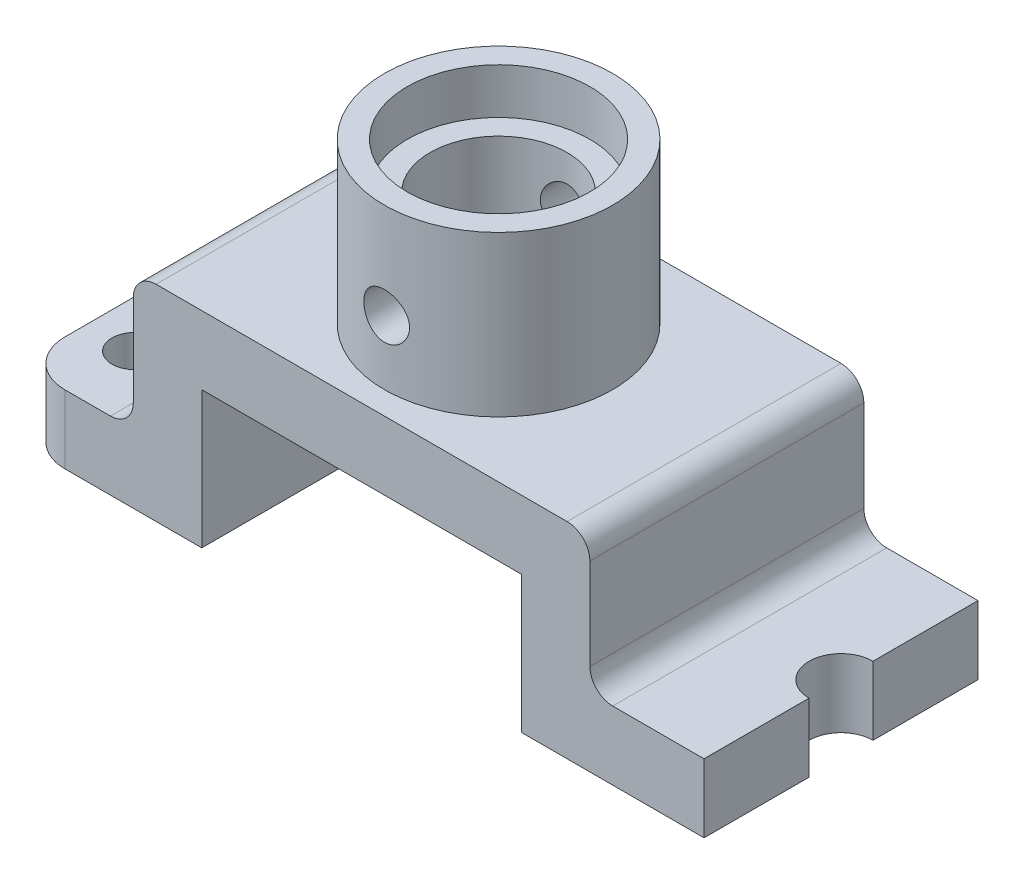
SolidWorks part; units mm, degrees
ref_plane "Front Plane" through (0, 0, 0) normal (0, 0, 1) x (1, 0, 0)
ref_plane "Top Plane" through (0, 0, 0) normal (0, 1, 0) x (1, 0, 0)
ref_plane "Right Plane" through (0, 0, 0) normal (1, 0, 0) x (0, 0, -1)
sketch "Sketch1" plane through (0, 0, 0) normal (0, 0, 1) x (1, 0, 0)
  line L1 (-75, 22.5) -> (75, 22.5)
  line L2 (-75, 22.5) -> (-75, -22.5)
  line L3 (-75, -22.5) -> (75, -22.5)
  line L4 (75, 22.5) -> (75, -22.5)
  line L5 (-75, 22.5) -> (75, -22.5) construction
  line L6 (-75, -22.5) -> (75, 22.5) construction
  point P0 (0, 0)
  dimension "D1" = 45
  dimension "D2" = 150
extrude "Boss-Extrude1" add sketch "Sketch1" along normal blind 60
sketch "Sketch2" plane through (0, 0, 60) normal (0, 0, 1) x (1, 0, 0)
  line L0 (-75, -22.5) -> (75, -22.5) construction
  line L1 (-35, 7.5) -> (35, 7.5)
  line L2 (-35, 7.5) -> (-35, -22.5)
  line L3 (-35, -22.5) -> (35, -22.5)
  line L4 (35, 7.5) -> (35, -22.5)
  line L5 (-75, 22.5) -> (-75, -22.5) construction
  dimension "D1" = 70
  dimension "D2" = 30
  dimension "D3" = 40
extrude "Cut-Extrude1" cut sketch "Sketch2" against normal blind 60
sketch "Sketch8" plane through (0, 22.5, 0) normal (0, 1, 0) x (1, 0, 0)
  line L0 (75, -60) -> (-75, -60) construction
  line L1 (-75, 0) -> (-50, 0)
  line L2 (-75, 0) -> (-75, -60)
  line L3 (-75, -60) -> (-50, -60)
  line L4 (-50, 0) -> (-50, -60)
  line L5 (75, 0) -> (-75, 0) construction
  line L6 (50, 0) -> (75, 0)
  line L7 (50, 0) -> (50, -60)
  line L8 (50, -60) -> (75, -60)
  line L9 (75, 0) -> (75, -60)
  line L10 (75, -60) -> (75, 0) construction
  dimension "D1" = 25
  dimension "D2" = 25
extrude "Cut-Extrude5" cut sketch "Sketch8" against normal blind 30
sketch "Sketch9" plane through (0, 22.5, 0) normal (0, 1, 0) x (1, 0, 0)
  line L0 (-75, 0) -> (-75, -60) construction
  line L1 (50, 0) -> (-50, 0) construction
  circle A0 centre (0, -30) radius 25
  dimension "D1" = 50
  dimension "D2" = 75
  dimension "D3" = 30
extrude "Boss-Extrude4" add sketch "Sketch9" along normal blind 35
sketch "Sketch10" plane through (0, 57.5, 0) normal (0, 1, 0) x (1, 0, 0)
  circle A0 centre (0, -30) radius 20
  circle A1 centre (0, -30) radius 15
  circle A2 centre (0, -30) radius 10
  dimension "D1" = 40
  dimension "D2" = 30
  dimension "D3" = 20
extrude "Cut-Extrude7" cut sketch "Sketch10" against normal blind 10 contours A0 A1 region at (-19.4343, 57.5, 30)
extrude "Cut-Extrude8" cut sketch "Sketch10<5>" against normal blind 70 contours A1 A2 | A2 region at (-14.5757, 57.5, 30) region at (0, 57.5, 30)
sketch "Sketch10<5>" plane through (0, 57.5, 0) normal (0, 1, 0) x (1, 0, 0) same geometry as "Sketch10"
sketch "Sketch12" plane through (0, 0, 60) normal (0, 0, 1) x (1, 0, 0)
  line L0 (20, 57.5) -> (-20, 57.5) construction
  line L1 (-25, 57.5) -> (-25, 22.5) construction
  circle A0 centre (0, 36.5) radius 5
  dimension "D1" = 10
  dimension "D2" = 21
  dimension "D3" = 25
extrude "Cut-Extrude9" cut sketch "Sketch12" against normal blind 70
fillet "Fillet1" radius 10 2 edges at (-75, -15, 60) (-75, -15, 0)
sketch "Sketch13" plane through (0, -7.5, 0) normal (0, 1, 0) x (1, 0, 0)
  line L0 (75, -60) -> (75, 0) construction
  line L1 (75, 0) -> (50, 0) construction
  circle A0 centre (75, -30) radius 7
  circle A1 centre (0, -30) radius 15 construction
  dimension "D1" = 75
  dimension "D2" = 30
extrude "Cut-Extrude10" cut sketch "Sketch13" against normal blind 15
sketch "Sketch14" plane through (0, -7.5, 0) normal (0, 1, 0) x (1, 0, 0)
  line L0 (-50, 0) -> (-65, 0) construction
  line L1 (-65, -60) -> (-50, -60) construction
  circle A0 centre (-64.6572, -15) radius 5
  circle A1 centre (-64.6572, -45) radius 5
  dimension "D1" = 15
  dimension "D2" = 15
  dimension "D3" = 30
extrude "Cut-Extrude11" cut sketch "Sketch14" against normal blind 15
fillet "Fillet2" radius 5 4 edges at (-50, -7.5, 30) (50, -7.5, 30) (50, 22.5, 30) (-50, 22.5, 30)
